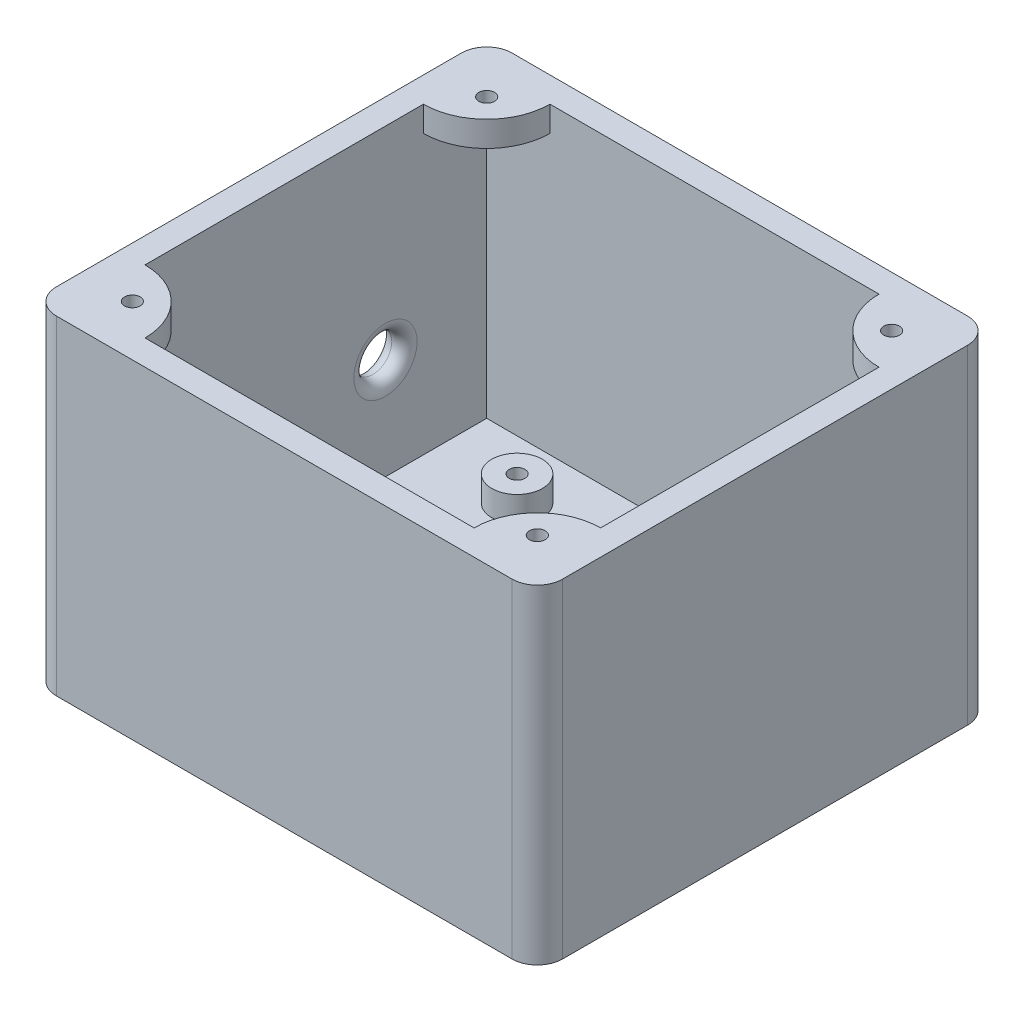
SolidWorks part; units mm, degrees
ref_plane "Front Plane" through (0, 0, 0) normal (0, 0, 1) x (1, 0, 0)
ref_plane "Top Plane" through (0, 0, 0) normal (0, 1, 0) x (1, 0, 0)
ref_plane "Right Plane" through (0, 0, 0) normal (1, 0, 0) x (0, 0, -1)
sketch "Sketch1" plane through (0, 0, 0) normal (0, 1, 0) x (1, 0, 0)
  line L0 (-5, 0) -> (0, 0) construction
  line L1 (0, 0) -> (90, 0)
  line L2 (0, 0) -> (0, 80)
  line L3 (0, 80) -> (90, 80)
  line L4 (90, 0) -> (90, 80)
  line L5 (-5, 85) -> (95, 85)
  line L6 (-5, 85) -> (-5, -5)
  line L7 (-5, -5) -> (95, -5)
  line L8 (95, 85) -> (95, -5)
  line L9 (0, 0) -> (0, -5) construction
  line L10 (90, 85) -> (90, 80) construction
  line L11 (90, 80) -> (95, 80) construction
  dimension "D1" = 90
  dimension "D2" = 5
  dimension "D3" = 80
extrude "Boss-Extrude1" add sketch "Sketch1" along normal blind 60
sketch "Sketch2" plane through (0, 0, 0) normal (0, -1, 0) x (-1, 0, 0)
  line L1 (5, -5) -> (-95, -5)
  line L2 (5, -5) -> (5, 85)
  line L3 (5, 85) -> (-95, 85)
  line L4 (-95, -5) -> (-95, 85)
extrude "Boss-Extrude2" add sketch "Sketch2" along normal blind 5
fillet "Fillet1" radius 5 4 edges at (-5, 27.5, -85) (95, 27.5, -85) (95, 27.5, 5) (-5, 27.5, 5)
sketch "Sketch3" plane through (0, 0, 0) normal (0, 1, 0) x (1, 0, 0)
  line L0 (17.5, 68.5) -> (17.5, 80) construction
  line L1 (90, 80) -> (0, 80) construction
  line L2 (17.5, 80) -> (0, 80) construction
  line L3 (72.5, 11.5) -> (72.5, 0) construction
  line L4 (0, 0) -> (90, 0) construction
  line L5 (72.5, 0) -> (90, 0) construction
  circle A0 centre (17.5, 68.5) radius 1.55
  circle A1 centre (17.5, 11.5) radius 1.55
  circle A2 centre (72.5, 11.5) radius 1.55
  circle A3 centre (72.5, 68.5) radius 1.55
  dimension "D3" = 3.1
  dimension "D1" = 57
  dimension "D2" = 55
extrude "Cut-Extrude1" cut sketch "Sketch3" against normal through all
sketch "Sketch4" plane through (0, -5, 0) normal (0, -1, 0) x (-1, 0, 0)
  circle A0 centre (-17.5, 11.5) radius 3
  circle A1 centre (-72.5, 11.5) radius 3
  circle A2 centre (-72.5, 68.5) radius 3
  circle A3 centre (-17.5, 68.5) radius 3
  dimension "D1" = 6
extrude "Cut-Extrude2" cut sketch "Sketch4" against normal blind 2.5
sketch "Sketch5" plane through (0, 0, 0) normal (0, 1, 0) x (1, 0, 0)
  line L0 (25, 65) -> (25, 15) construction
  line L1 (26, 65) -> (26, 15)
  line L2 (24, 65) -> (24, 15)
  line L3 (25, 65) -> (25, 80) construction
  line L6 (90, 80) -> (0, 80) construction
  line L7 (25, 15) -> (25, 0) construction
  line L8 (0, 0) -> (90, 0) construction
  line L9 (65, 65) -> (65, 15) construction
  line L11 (66, 65) -> (66, 15)
  line L12 (64, 65) -> (64, 15)
  line L13 (65, 65) -> (65, 80) construction
  line L14 (65, 15) -> (65, 0) construction
  line L15 (90, 80) -> (0, 80) construction
  line L16 (0, 0) -> (90, 0) construction
  line L17 (24, 65) -> (26, 65) construction
  line L18 (51.6667, 65) -> (51.6667, 15) construction
  line L19 (52.6667, 65) -> (52.6667, 15)
  line L20 (50.6667, 65) -> (50.6667, 15)
  line L21 (51.6667, 65) -> (51.6667, 80) construction
  line L22 (51.6667, 15) -> (51.6667, 0) construction
  line L23 (38.3333, 65) -> (38.3333, 15) construction
  line L24 (39.3333, 65) -> (39.3333, 15)
  line L25 (37.3333, 65) -> (37.3333, 15)
  line L26 (38.3333, 65) -> (38.3333, 80) construction
  line L27 (38.3333, 15) -> (38.3333, 0) construction
  line L28 (51.6667, 80) -> (65, 80) construction
  line L29 (38.3333, 80) -> (25, 80) construction
  line L30 (38.3333, 80) -> (51.6667, 80) construction
  line L31 (37.3333, 65) -> (39.3333, 65) construction
  line L32 (50.6667, 65) -> (52.6667, 65) construction
  line L33 (64, 65) -> (66, 65) construction
  line L34 (65, 80) -> (90, 80) construction
  line L35 (25, 80) -> (0, 80) construction
  arc A0 (26, 65) -> (24, 65) centre (25, 65) ccw
  arc A1 (24, 15) -> (26, 15) centre (25, 15) ccw
  arc A2 (66, 65) -> (64, 65) centre (65, 65) ccw
  arc A3 (64, 15) -> (66, 15) centre (65, 15) ccw
  arc A4 (52.6667, 65) -> (50.6667, 65) centre (51.6667, 65) ccw
  arc A5 (50.6667, 15) -> (52.6667, 15) centre (51.6667, 15) ccw
  arc A6 (39.3333, 65) -> (37.3333, 65) centre (38.3333, 65) ccw
  arc A7 (37.3333, 15) -> (39.3333, 15) centre (38.3333, 15) ccw
  point P2 (25, 40)
  point P19 (65, 40)
  point P37 (51.6667, 40)
  point P48 (38.3333, 40)
  dimension "D1" = 1
  dimension "D2" = 15
  dimension "D3" = 25
extrude "Cut-Extrude3" cut sketch "Sketch5" against normal through all
sketch "Sketch6" plane through (0, 0, -80) normal (0, 0, 1) x (1, 0, 0)
  line L0 (0, 60) -> (12.5, 60)
  line L1 (90, 60) -> (0, 60) construction
  line L3 (0, 60) -> (0, 0) construction
  line L4 (0, 55) -> (0, 60)
  line L5 (0, 55) -> (12.5, 55)
  line L6 (12.5, 55) -> (12.5, 60)
  dimension "D1" = 12.5
  dimension "D2" = 5
revolve "Revolve2" add sketch "Sketch6" angle 90 about axis through (0, 60, -80) along (0, -1, 0)
sketch "Sketch7" plane through (0, 0, -80) normal (0, 0, 1) x (1, 0, 0)
  line L1 (90, 60) -> (77.5, 60)
  line L2 (90, 60) -> (90, 55)
  line L3 (90, 55) -> (77.5, 55)
  line L4 (77.5, 60) -> (77.5, 55)
  dimension "D1" = 12.5
  dimension "D2" = 5
revolve "Revolve3" add sketch "Sketch7" angle 90 about axis through (90, 60, -80) along (0, -1, 0) reverse direction yes
sketch "Sketch8" plane through (0, 0, 0) normal (0, 0, -1) x (-1, 0, 0)
  line L1 (-90, 60) -> (-77.5, 60)
  line L2 (-90, 60) -> (-90, 55)
  line L3 (-90, 55) -> (-77.5, 55)
  line L4 (-77.5, 60) -> (-77.5, 55)
  dimension "D1" = 5
  dimension "D2" = 12.5
revolve "Revolve4" add sketch "Sketch8" angle 90 about axis through (90, 60, 0) along (0, -1, 0)
sketch "Sketch9" plane through (0, 0, 0) normal (0, 0, -1) x (-1, 0, 0)
  line L1 (0, 60) -> (-12.5, 60)
  line L2 (0, 60) -> (0, 55)
  line L3 (0, 55) -> (-12.5, 55)
  line L4 (-12.5, 60) -> (-12.5, 55)
  dimension "D1" = 12.5
  dimension "D2" = 5
revolve "Revolve5" add sketch "Sketch9" angle 90 about axis through (0, 60, 0) along (0, -1, 0) reverse direction yes
sketch "Sketch10" plane through (0, 60, 0) normal (0, 1, 0) x (1, 0, 0)
  line L0 (5, 75) -> (85, 75) construction
  line L1 (85, 75) -> (85, 5) construction
  line L2 (85, -5) -> (85, 85) construction
  line L4 (90, 85) -> (0, 85) construction
  line L6 (0, -5) -> (90, -5) construction
  line L8 (-5, 75) -> (95, 75) construction
  line L10 (95, 0) -> (95, 80) construction
  line L11 (-5, 80) -> (-5, 0) construction
  circle A0 centre (5, 75) radius 1.55
  circle A1 centre (85, 75) radius 1.55
  circle A2 centre (85, 5) radius 1.55
  circle A3 centre (5, 5) radius 1.55
  point P8 (0, 0)
  point P13 (85, 40)
  point P18 (-5, 76.25)
  point P23 (45, 75)
  dimension "D2" = 3.1
  dimension "D1" = 80
  dimension "D3" = 70
extrude "Cut-Extrude5" cut sketch "Sketch10" against normal blind 5
sketch "Sketch12" plane through (-5, 0, 0) normal (-1, 0, 0) x (0, 0, 1)
  line L8 (-80, 60) -> (-80, -5) construction
  line L9 (0, -5) -> (-80, -5) construction
  circle A0 centre (-60, 20) radius 3.75
  dimension "D3" = 7.5
  dimension "D1" = 20
  dimension "D2" = 25
extrude "Cut-Extrude6" cut sketch "Sketch12" against normal blind 5
fillet "Fillet2" radius 2.5 2 edges at (0, 20, -56.25) (-5, 20, -56.25)
sketch "Sketch13" plane through (0, 0, 0) normal (0, 1, 0) x (1, 0, 0)
  circle A0 centre (17.5, 68.5) radius 5
  circle A1 centre (72.5, 68.5) radius 5
  circle A2 centre (72.5, 11.5) radius 5
  circle A3 centre (17.5, 11.5) radius 5
  dimension "D1" = 10
extrude "Boss-Extrude3" add sketch "Sketch13" along normal blind 5
sketch "Sketch14" plane through (0, 0, 0) normal (0, -1, 0) x (-1, 0, 0)
  circle A0 centre (-72.5, 68.5) radius 1.55
  circle A1 centre (-72.5, 11.5) radius 1.55
  circle A2 centre (-17.5, 11.5) radius 1.55
  circle A3 centre (-17.5, 68.5) radius 1.55
extrude "Cut-Extrude7" cut sketch "Sketch14" against normal through all
